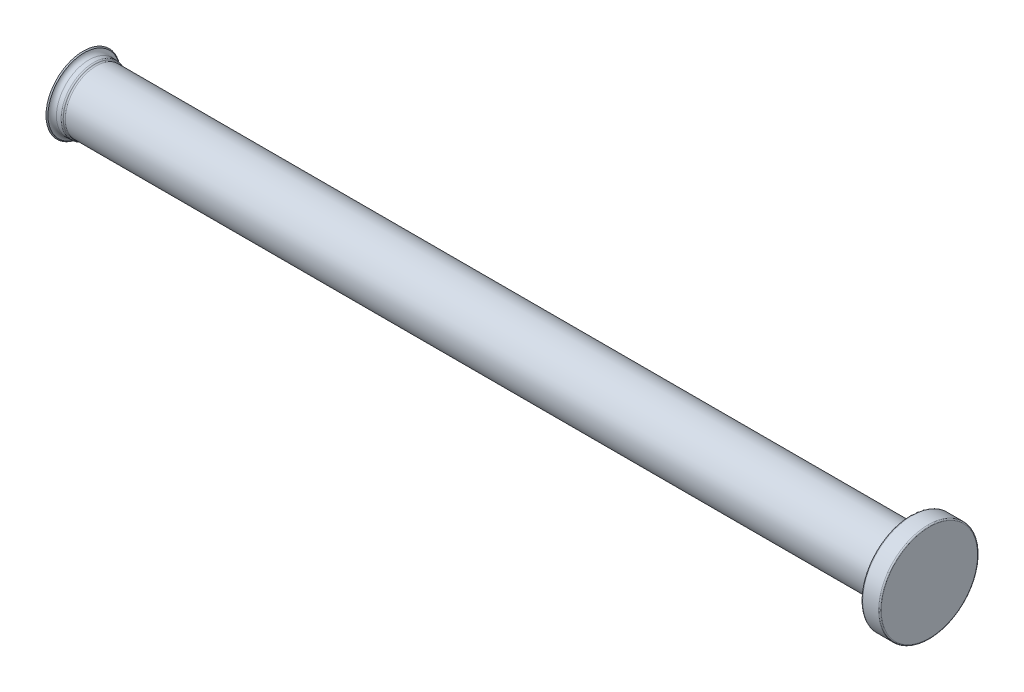
SolidWorks part; units mm, degrees
material "AISI 304"
ref_plane "Ön Düzlem" through (0, 0, 0) normal (0, 0, 1) x (1, 0, 0)
ref_plane "Üst Düzlem" through (0, 0, 0) normal (0, 1, 0) x (1, 0, 0)
ref_plane "Sağ Düzlem" through (0, 0, 0) normal (1, 0, 0) x (0, 0, -1)
sketch "Çizim1" plane through (0, 0, 0) normal (0, 0, 1) x (1, 0, 0)
  line L0 (0, 0) -> (-67.5, 0)
  line L1 (0, 0) -> (0, 4)
  line L2 (0, 4) -> (-1.5, 4)
  line L3 (-1.5, 4) -> (-1.5, 2.5)
  line L4 (-1.5, 2.5) -> (-67.5, 2.5)
  line L5 (0, 0) -> (21.8777, 0) construction
  line L6 (-67.5, 2.5) -> (-67.5, 0)
  dimension "D1" = 5
  dimension "D2" = 1.5
  dimension "D3" = 8
  dimension "D4" = 66
revolve "Döndür1" add sketch "Çizim1" angle 360 about L5
fillet "Radyus1" radius 0.1 2 edges at (0, 0, 4) (-1.5, 0, 4)
sketch "Çizim3" plane through (-67.5, 0, 0) normal (-1, 0, 0) x (0, 0, 1)
  circle A1 centre (0, 0) radius 2.5
  circle A2 centre (0, 0) radius 2.5
  dimension "D1" = 0
extrude "Kes-Ekstrüzyon1" cut sketch "Çizim3" against normal blind 10 draft 80
sketch "Çizim4" plane through (0, 0, 0) normal (0, 0, 1) x (1, 0, 0)
  line L0 (-67.5, 2.5) -> (-67.5, -2.5) construction
  line L1 (-67.5, 2.5) -> (-67.5, -2.5) construction
  line L2 (-67.5, 2.5) -> (-68, 2.5) construction
  line L3 (-68.5081, 2.8924) -> (-68.387, 2.9241) construction
  line L4 (-68, 2.5) -> (-67.6221, 2.5)
  line L5 (-67.6252, 2.6252) -> (-68, 2.6252)
  line L6 (-68.5081, 2.8924) -> (-68.4716, 3)
  line L7 (-68.4716, 3) -> (-68.387, 2.9241)
  line L8 (-68.4716, 3) -> (-68.4476, 2.9082) construction
  line L9 (-1.5, 3.9) -> (-1.5, -3.9) construction
  line L10 (-67.5, 0) -> (-55.9233, 0) construction
  line L11 (-67.5, 2.5) -> (-67.5, 2.4026) construction
  line L15 (-67.4083, 2.0006) -> (-67.5, 2.4026)
  line L16 (-67.4083, 2.5) -> (-67.4083, 2.0006)
  line L17 (-1.5, 2.5) -> (-67.5, 2.5) construction
  line L18 (-1.5, 2.5) -> (-67.5, 2.5) construction
  arc A0 (-68, 2.5) -> (-68.5081, 2.8924) centre (-68, 3.0252) cw
  arc A1 (-67.6221, 2.5) -> (-67.5, 2.4026) centre (-67.6221, 2.3748) cw
  arc A2 (-67.5, 2.5) -> (-67.6252, 2.6252) centre (-67.6252, 2.5) ccw construction
  arc A3 (-68, 2.6252) -> (-68.387, 2.9241) centre (-68, 3.0252) cw
  arc A4 (-67.6252, 2.6252) -> (-67.5168, 2.5626) centre (-67.6252, 2.5) cw
  arc A5 (-67.5168, 2.5626) -> (-67.4083, 2.5) centre (-67.4083, 2.6252) ccw
  dimension "D2" = 0.4
  dimension "D3" = 0.1252
  dimension "D1" = 66.5
  dimension "D4" = 0.0846
  dimension "D5" = 6
  dimension "D6" = 0.4994
revolve "Döndür2" add sketch "Çizim4" angle 360 about L10
ref_axis "Eksen1" through (2.6004, 0, 0) along (-1, 0, 0)
